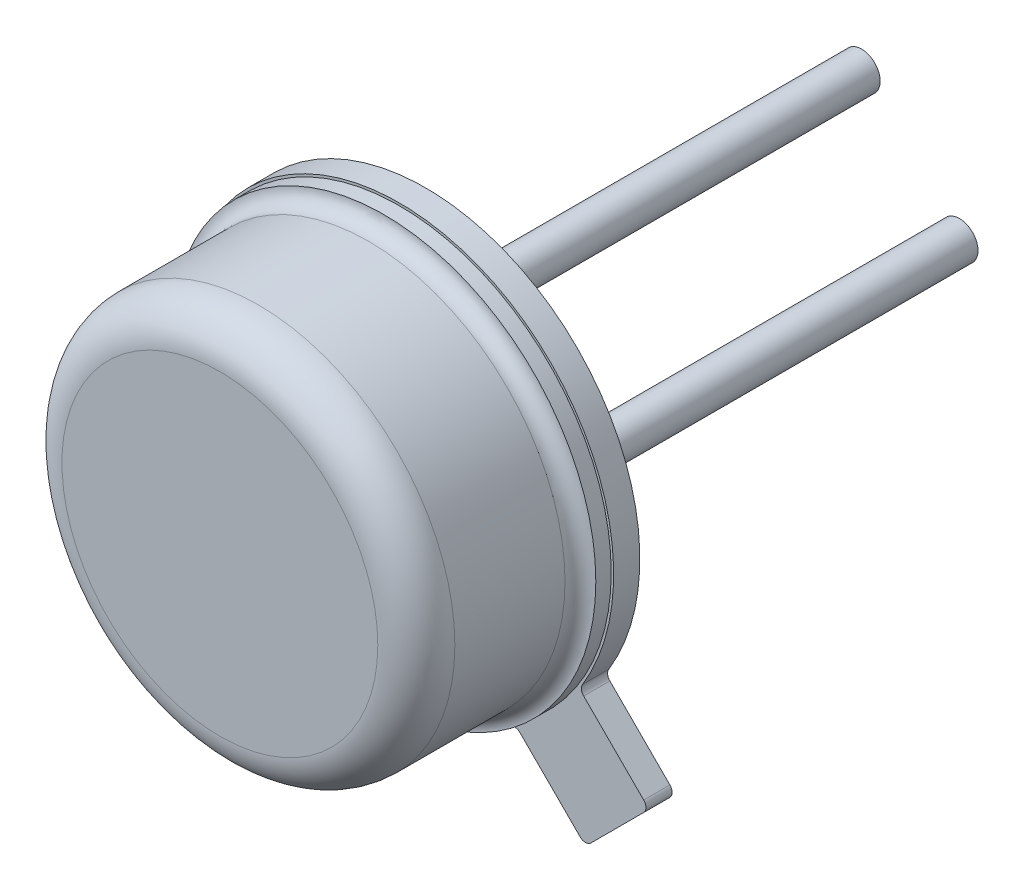
SolidWorks part; units mm, degrees
ref_plane "Front Plane" through (0, 0, 0) normal (0, 0, 1) x (1, 0, 0)
ref_plane "Top Plane" through (0, 0, 0) normal (0, 1, 0) x (1, 0, 0)
ref_plane "Right Plane" through (0, 0, 0) normal (1, 0, 0) x (0, 0, -1)
sketch "Sketch1" plane through (0, 0, 0) normal (0, 0, 1) x (1, 0, 0)
  line L0 (97.9756, 63.5081) -> (97.9756, 60.7266) construction
  line L1 (97.9756, 60.7266) -> (100.7571, 60.7266) construction
  line L2 (97.9756, 60.7266) -> (99.9424, 58.7597) construction
  line L3 (99.542, 58.3343) -> (100.3207, 57.5555)
  line L4 (100.3679, 59.1602) -> (101.1466, 58.3814)
  line L5 (97.5627, 60.3136) -> (98.3886, 61.1395) construction
  line L6 (100.4622, 57.5555) -> (101.1466, 58.24)
  arc A0 (100.3531, 59.2828) -> (99.4193, 58.3491) centre (97.9756, 60.7266) ccw
  circle A1 centre (97.9756, 61.9966) radius 0.2415
  circle A2 centre (99.2456, 60.7266) radius 0.2415
  circle A3 centre (96.7056, 60.7266) radius 0.2415
  arc A5 (99.542, 58.3343) -> (99.4193, 58.3491) centre (99.4712, 58.2636) ccw
  arc A6 (100.3531, 59.2828) -> (100.3679, 59.1602) centre (100.4386, 59.2309) ccw
  arc A7 (100.3207, 57.5555) -> (100.4622, 57.5555) centre (100.3914, 57.6263) ccw
  arc A8 (101.1466, 58.24) -> (101.1466, 58.3814) centre (101.0759, 58.3107) ccw
extrude "Boss-Extrude1" add sketch "Sketch1" along normal blind 0.34
sketch "Sketch2" plane through (0, 0, 0.34) normal (0, 0, 1) x (1, 0, 0)
  circle A0 centre (97.9756, 60.7266) radius 2.75
extrude "Boss-Extrude2" add sketch "Sketch2" along normal blind 0.2
sketch "Sketch3" plane through (0, 0, 0.54) normal (0, 0, 1) x (1, 0, 0)
  circle A3 centre (97.9756, 60.7266) radius 2.55
  circle A4 centre (97.9756, 60.7266) radius 2.55
  dimension "D1" = 0.2
extrude "Boss-Extrude3" add sketch "Sketch3" along normal blind 2.13
fillet "Fillet1" radius 0.2 1 edges at (100.5256, 60.7266, 0.54)
fillet "Fillet2" radius 0.5 1 edges at (100.5256, 60.7266, 2.67)
sketch "Sketch4" plane through (0, 0, 0.34) normal (0, 0, -1) x (-1, 0, 0)
  circle A2 centre (-99.2456, 60.7266) radius 0.241
  circle A3 centre (-97.9756, 61.9966) radius 0.241
  circle A4 centre (-96.7056, 60.7266) radius 0.241
  dimension "D2" = 0.482
  dimension "D1" = 0.482
  dimension "D3" = 0.482
extrude "Boss-Extrude4" add sketch "Sketch4" along normal blind 6
